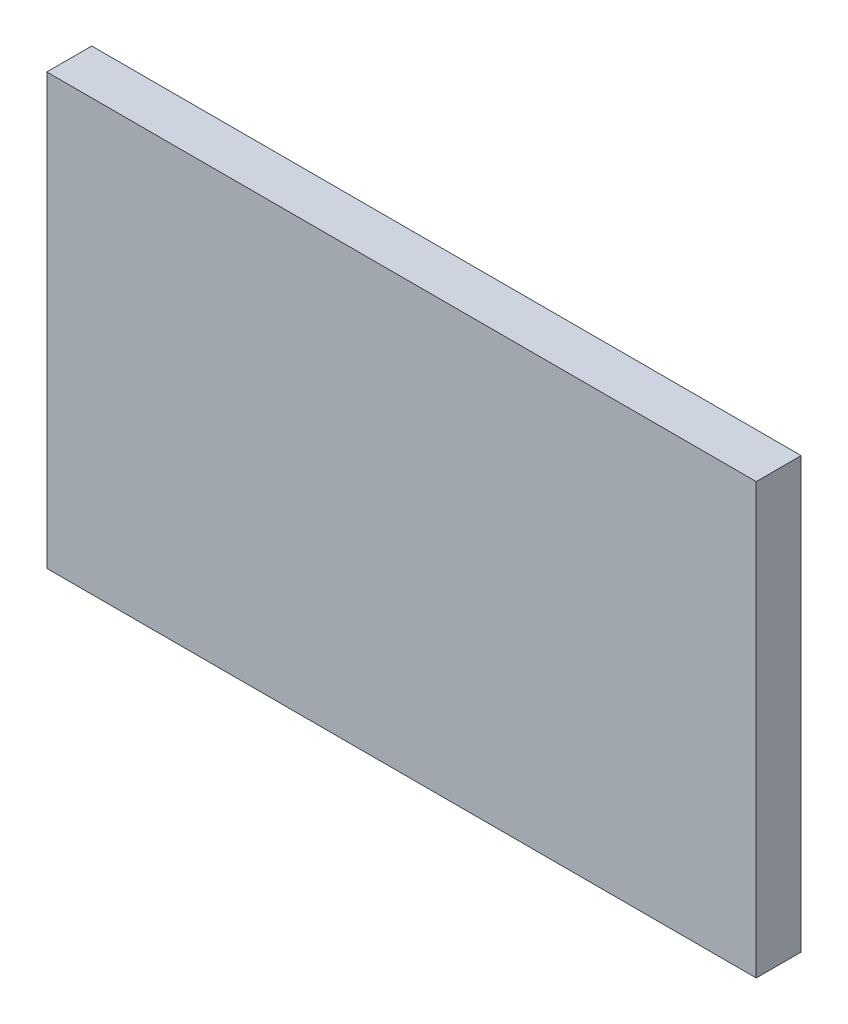
SolidWorks part; units mm, degrees
ref_plane "Front Plane" through (0, 0, 0) normal (0, 0, 1) x (1, 0, 0)
ref_plane "Top Plane" through (0, 0, 0) normal (0, 1, 0) x (1, 0, 0)
ref_plane "Right Plane" through (0, 0, 0) normal (1, 0, 0) x (0, 0, -1)
sketch "Sketch1" plane through (0, 0, 0) normal (0, 0, 1) x (1, 0, 0)
  line L0 (150.5526, 94.5488) -> (-142.0044, -82.7375) construction
  line L1 (150.5526, -82.7375) -> (-142.0044, -82.7375)
  line L2 (150.5526, -82.7375) -> (150.5526, 94.5488)
  line L3 (150.5526, 94.5488) -> (-142.0044, 94.5488)
  line L4 (-142.0044, -82.7375) -> (-142.0044, 94.5488)
  line L5 (-142.0044, 94.5488) -> (150.5526, -82.7375) construction
  arc A2 (-135.8953, -27.9439) -> (-104.3843, -82.6415) centre (-106.976, -47.7091) ccw construction
  arc A5 (150.1834, 82.3974) -> (135.9464, 93.0803) centre (141.0276, 85.0238) ccw construction
  point P0 (0, 0)
extrude "Boss-Extrude1" add sketch "Sketch1" against normal blind 18.542
